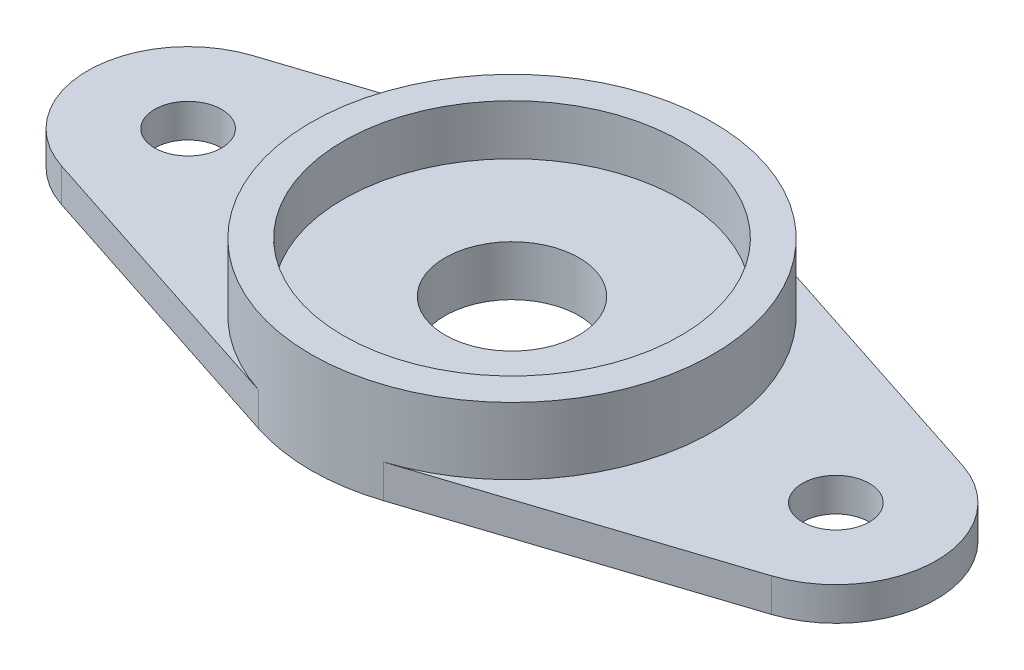
SolidWorks part; units mm, degrees
ref_plane "Front Plane" through (0, 0, 0) normal (0, 0, 1) x (1, 0, 0)
ref_plane "Top Plane" through (0, 0, 0) normal (0, 1, 0) x (1, 0, 0)
ref_plane "Right Plane" through (0, 0, 0) normal (1, 0, 0) x (0, 0, -1)
sketch "Sketch1" plane through (0, 0, 0) normal (0, 1, 0) x (1, 0, 0)
  line L2 (2.7921, -8.5559) -> (15.9011, -4.278)
  line L3 (15.9011, 4.278) -> (2.7921, 8.5559)
  line L4 (-14.505, 0) -> (14.505, 0) construction
  line L5 (-15.9011, 4.278) -> (-2.7921, 8.5559)
  line L6 (-15.9011, -4.278) -> (-2.7921, -8.5559)
  circle A0 centre (0, 0) radius 9
  circle A1 centre (0, 0) radius 7.55
  arc A2 (-15.9011, 4.278) -> (-15.9011, -4.278) centre (-14.505, 0) ccw
  arc A3 (15.9011, -4.278) -> (15.9011, 4.278) centre (14.505, 0) ccw
  circle A4 centre (-14.505, 0) radius 1.5
  circle A5 centre (14.505, 0) radius 1.5
  circle A6 centre (0, 0) radius 7.5 construction
  circle A7 centre (0, 0) radius 3
  point P12 (0, 0)
  dimension "D1" = 3
  dimension "D2" = 3
  dimension "D3" = 15.1
  dimension "D4" = 3
  dimension "D5" = 1.5
  dimension "D6" = 15
  dimension "D7" = 29.01
  dimension "D8" = 6
extrude "Boss-Extrude1" add sketch "Sketch1" along normal blind 4.4972 contours L5 A2 L6 A0 A4 | A1 | A0 A1 | L2 A3 L3 A0 A5 region at (12.2943, 0, 0) region at (0, 0, 8.7454) region at (-12.2943, 0, 0) region at (-7.3365, 0, 0)
extrude "Cut-Extrude2" cut sketch "Sketch1<6>" against normal blind 2.25 from surface contours A1 region at (-7.3365, 0, 0) starting at face at (-14.505, 4.4972, 1.5)
sketch "Sketch1<6>" plane through (0, 0, 0) normal (0, 1, 0) x (1, 0, 0) same geometry as "Sketch1"
extrude "Cut-Extrude1" cut sketch "Sketch1<5>" against normal blind 2.9972 from surface contours L5 A2 L6 A0 A4 | L2 A3 L3 A0 A5 region at (12.2943, 0, 0) region at (-12.2943, 0, 0) starting at face at (0, 4.4972, 7.55)
sketch "Sketch1<5>" plane through (0, 0, 0) normal (0, 1, 0) x (1, 0, 0) same geometry as "Sketch1"
equation "\"wallthickness\"= .118in"
equation "\"floorThickness\"= .220in"
equation "\"D1@Boss-Extrude1\"=\"wallthickness\"+1.5mm"
equation "\"D1@Cut-Extrude1\"=\"wallthickness\""
